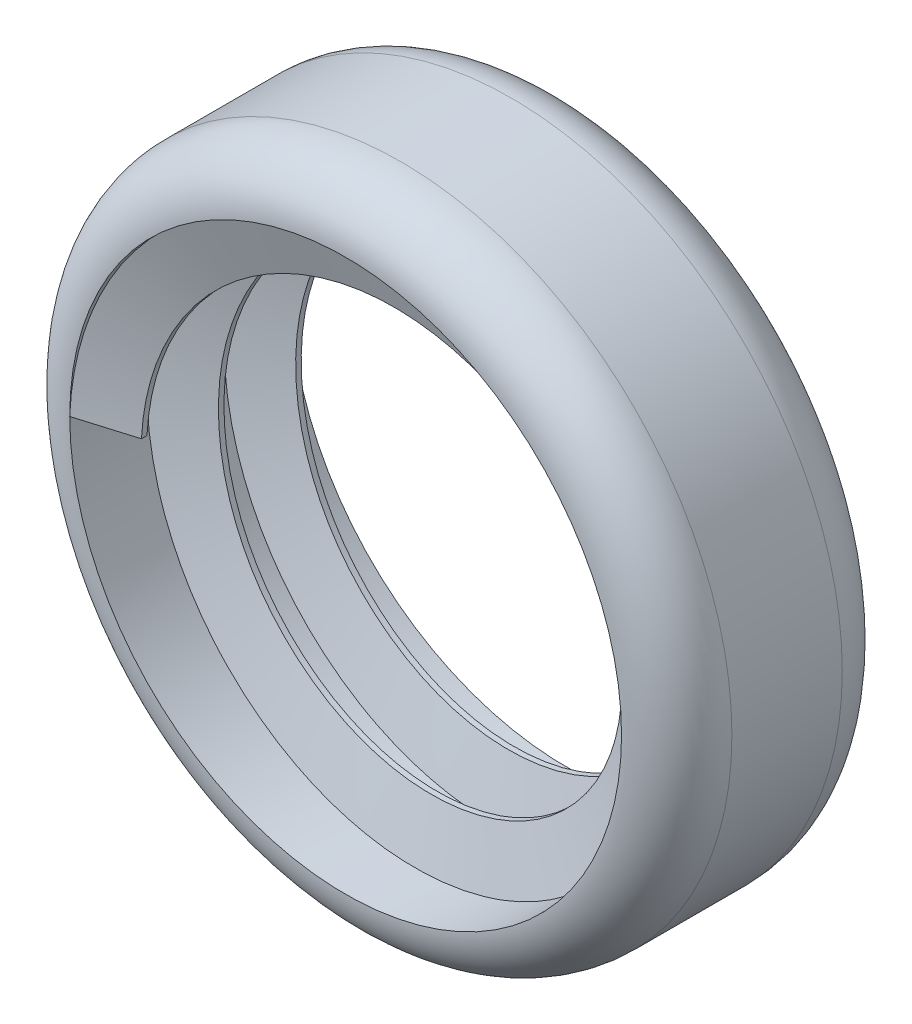
SolidWorks part; units mm, degrees
ref_plane "Płaszczyzna przednia" through (0, 0, 0) normal (0, 0, 1) x (1, 0, 0)
ref_plane "Płaszczyzna górna" through (0, 0, 0) normal (0, 1, 0) x (1, 0, 0)
ref_plane "Płaszczyzna prawa" through (0, 0, 0) normal (1, 0, 0) x (0, 0, -1)
sketch "Szkic1" plane through (0, 0, 0) normal (0, 0, 1) x (1, 0, 0)
  circle A0 centre (0, 0) radius 6
  circle A1 centre (0, 0) radius 5
  dimension "D1" = 12
  dimension "D2" = 10
extrude "Dodanie-wyciągnięcie1" add sketch "Szkic1" along normal blind 4
ref_plane "Płaszczyzna1" through (0, 0, 4) normal (0, 0, 1) x (1, 0, 0)
sketch "Szkic4" plane through (0, 0, 4) normal (0, 0, 1) x (1, 0, 0)
  circle A0 centre (0, 0) radius 5
curve "Helisa/Spirala2" pitch 1.4 height 3.5 radius 5 centre (0, 0, 4) axis (0, 0, -1) start towards (-1, 0, 0)
sketch "Szkic8" plane through (0, 0, 0) normal (0, 1, 0) x (1, 0, 0)
  line L0 (-5, -3.3) -> (-5, -4)
  line L4 (-5, -4) -> (5, -4) construction
  line L5 (-5, -4) -> (-4, -3.7)
  line L6 (-4, -3.7) -> (-4, -3.6)
  line L7 (-4, -3.6) -> (-5, -3.3)
  spline S0 degree 3 poles (-5, -4) (-5, -3.971) (-4.7397, -3.9124) (-3.6276, -3.825) (-1.9632, -3.7375) (0, -3.65) (1.9632, -3.5625) (3.6276, -3.475) (4.7397, -3.3875) (5.1302, -3.3) (4.7397, -3.2125) (3.6276, -3.125) (1.9632, -3.0375) (0, -2.95) (-1.9632, -2.8625) (-3.6276, -2.775) (-4.7397, -2.6875) (-5.1302, -2.6) (-4.7397, -2.5125) (-3.6276, -2.425) (-1.9632, -2.3375) (0, -2.25) (1.9632, -2.1625) (3.6276, -2.075) (4.7397, -1.9875) (5.1302, -1.9) (4.7397, -1.8125) (3.6276, -1.725) (1.9632, -1.6375) (0, -1.55) (-1.9632, -1.4625) (-3.6276, -1.375) (-4.7397, -1.2875) (-5.1302, -1.2) (-4.7397, -1.1125) (-3.6276, -1.025) (-1.9632, -0.9375) (0, -0.85) (1.9632, -0.7625) (3.6276, -0.675) (4.7397, -0.5876) (5, -0.529) (5, -0.5) knots 0 0 0 0 0.025 0.05 0.075 0.1 0.125 0.15 0.175 0.2 0.225 0.25 0.275 0.3 0.325 0.35 0.375 0.4 0.425 0.45 0.475 0.5 0.525 0.55 0.575 0.6 0.625 0.65 0.675 0.7 0.725 0.75 0.775 0.8 0.825 0.85 0.875 0.9 0.925 0.95 0.975 1 1 1 1 construction
  dimension "D1" = 0.1
  dimension "D2" = 0.7
  dimension "D3" = 1
sweep "Wyciągnięcie po ścieżce2" add profiles "Szkic8" path "Helisa/Spirala2"
ref_plane "Płaszczyzna2" through (0, 6, 0) normal (0, 1, 0) x (1, 0, 0)
sketch "Szkic10" plane through (0, 6, 0) normal (0, 1, 0) x (1, 0, 0)
  line L0 (-6.6, -4) -> (6.6, -4) construction
  line L1 (-6, 0) -> (6, 0)
  line L2 (-6, 0) -> (-6, -4)
  line L3 (-6, -4) -> (6, -4)
  line L4 (6, 0) -> (6, -4)
  line L5 (6, -4) -> (6, 0) construction
  line L7 (-8.3392, 1.8366) -> (8.0306, 1.8366)
  line L8 (-8.3392, 1.8366) -> (-8.3392, -6.2971)
  line L9 (-8.3392, -6.2971) -> (8.0306, -6.2971)
  line L10 (8.0306, 1.8366) -> (8.0306, -6.2971)
extrude "Wytnij-wyciągnięcie3" cut sketch "Szkic10" against normal blind 15
fillet "Zaokrąglenie1" radius 1 2 edges at (6, 0, 4) (6, 0, 0)
